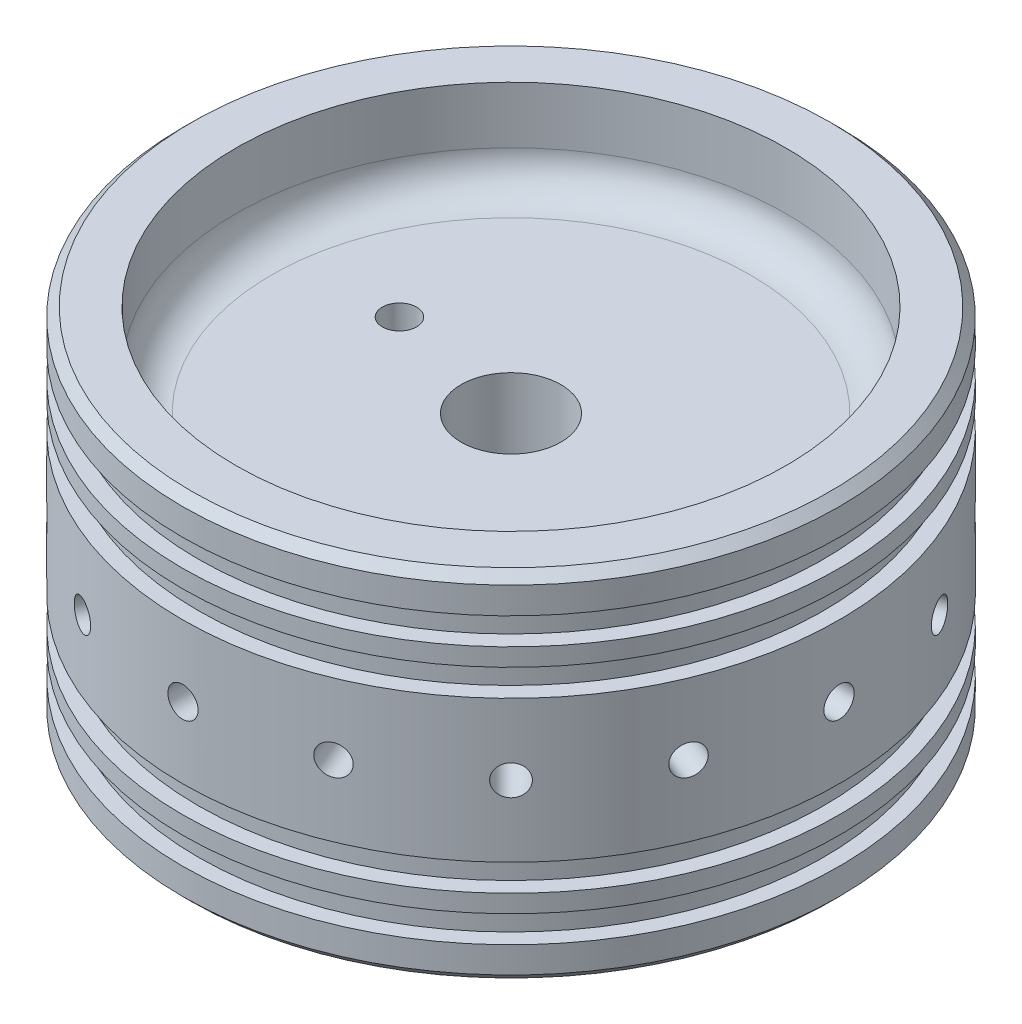
SolidWorks part; units mm, degrees
material "6061-T6 (SS)"
ref_plane "Front Plane" through (0, 0, 0) normal (0, 0, 1) x (1, 0, 0)
ref_plane "Top Plane" through (0, 0, 0) normal (0, 1, 0) x (1, 0, 0)
ref_plane "Right Plane" through (0, 0, 0) normal (1, 0, 0) x (0, 0, -1)
sketch "Sketch1" plane through (0, 0, 0) normal (0, 0, 1) x (1, 0, 0)
  line L11 (0, 0) -> (-58.7375, 0)
  line L13 (-58.7375, 31.8262) -> (-49.2125, 31.8262)
  line L14 (0, 0) -> (0, 15.3162)
  line L15 (0, 15.3162) -> (-49.2125, 15.3162)
  line L16 (-49.2125, 15.3162) -> (-49.2125, 31.8262)
  line L17 (0, 0) -> (0, -15.24)
  line L19 (-58.7375, -31.75) -> (-49.2125, -31.75)
  line L20 (-49.2125, -31.75) -> (-49.2125, -15.24)
  line L21 (-49.2125, -15.24) -> (0, -15.24)
  line L22 (0, 31.75) -> (0, -31.75) construction
  line L23 (-58.7375, 0) -> (-58.7375, 12.7)
  line L24 (-58.7375, 12.7) -> (-55.9181, 12.7)
  line L25 (-55.9181, 12.7) -> (-55.9181, 17.5006)
  line L26 (-55.9181, 17.5006) -> (-58.7375, 17.5006)
  line L27 (-58.7375, 17.5006) -> (-58.7375, 20.6756)
  line L28 (-58.7375, 20.6756) -> (-55.9181, 20.6756)
  line L29 (-55.9181, 20.6756) -> (-55.9181, 25.4762)
  line L30 (-55.9181, 25.4762) -> (-58.7375, 25.4762)
  line L31 (-58.7375, 25.4762) -> (-58.7375, 31.8262)
  line L32 (-58.7375, 0) -> (-58.7375, -12.7)
  line L33 (-58.7375, -12.7) -> (-55.9435, -12.7)
  line L34 (-55.9435, -12.7) -> (-55.9435, -17.5006)
  line L35 (-55.9435, -17.5006) -> (-58.7375, -17.5006)
  line L36 (-58.7375, -17.5006) -> (-58.7375, -20.6756)
  line L37 (-58.7375, -20.6756) -> (-55.9435, -20.6756)
  line L38 (-55.9435, -20.6756) -> (-55.9435, -25.4762)
  line L39 (-55.9435, -25.4762) -> (-58.7375, -25.4762)
  line L40 (-58.7375, -25.4762) -> (-58.7375, -31.75)
  dimension "D1" = 58.7375
  dimension "D2" = 12.7
  dimension "D3" = 4.8006
  dimension "D4" = 4.8006
  dimension "D5" = 3.175
  dimension "D6" = 2.8194
  dimension "D7" = 2.8194
  dimension "D8" = 9.525
  dimension "D9" = 12.7
  dimension "D10" = 4.8006
  dimension "D11" = 4.8006
  dimension "D12" = 3.175
  dimension "D13" = 2.794
  dimension "D14" = 2.794
  dimension "D16" = 9.525
revolve "Revolve1" add sketch "Sketch1" angle 360 about L22 region at (-32.4101, -9.7542, 0) region at (-32.3913, 9.7876, 0)
ref_plane "HoleFacePlane" through (0, 0, 58.7375) normal (0, 0, 1) x (1, 0, 0)
sketch "HoleReference" plane through (0, 0, 58.7375) normal (0, 0, 1) x (1, 0, 0)
  point P0 (0, 0)
hole_wizard "Tap Drill for 1/4-28 Tap1" positions "Sketch3" profile "Sketch4" hole size "1/4-28" standard "ANSI Inch"
sketch "Sketch3" plane through (0, 0, 58.7375) normal (0, 0, 1) x (1, 0, 0)
  point P0 (0, 0)
sketch "Sketch4" plane through (0, 0, 58.7375) normal (1, 0, 0) x (0, -1, 0)
  line L0 (0, 0) -> (0, 20.6754)
  line L1 (0, 20.6754) -> (2.7051, 19.05)
  line L2 (2.7051, 19.05) -> (2.7051, 0)
  line L5 (2.7051, 0) -> (0, 0)
  line L10 (0, 20.6754) -> (-2.7051, 19.05) construction
  line L11 (0, -6.35) -> (0, 107.95) construction
  dimension "Hole Dia." = 5.4102
  dimension "Hole Depth" = 19.05
  dimension "Drill Angle" = 118
ref_axis "Centerline" through (0, -12.7, 0) along (0, 1, 0)
pattern_circular "HolePattern" count 16 over 360 about axis through (0, -12.7, 0) along (0, 1, 0) of "Tap Drill for 1/4-28 Tap1"
chamfer "Chamfer2" distance 1.5875 angle 45 2 edges at (0, 31.8262, 58.7375) (0, -31.75, 58.7375)
fillet "Fillet1" radius 6.35 2 edges at (0, 15.3162, 49.2125) (0, -15.24, 49.2125)
sketch "CNVAReference" plane through (0, 15.3162, 0) normal (0, 1, 0) x (1, 0, 0)
  point P0 (0, 0)
sketch "InjectorReference" plane through (0, -15.24, 0) normal (0, -1, 0) x (1, 0, 0)
  point P0 (0, 0)
hole_wizard "Pipe Tap Drill for 1/2 Tap1" positions "Sketch7" profile "Sketch8" hole size "1/2" standard "ANSI Inch" end condition through all
sketch "Sketch7" plane through (0, 15.3162, 0) normal (0, 1, 0) x (1, 0, 0)
  point P0 (0, 0)
sketch "Sketch8" plane through (0, 15.3162, 0) normal (1, 0, 0) x (0, 0, 1)
  line L0 (0, 0) -> (0, 47.0662)
  line L1 (0, 47.0662) -> (8.9281, 47.0662)
  line L2 (8.9281, 47.0662) -> (8.9281, 0)
  line L5 (8.9281, 0) -> (0, 0)
  line L11 (0, -6.35) -> (0, 107.95) construction
  dimension "Thru Hole Dia." = 17.8562
  dimension "Thru Hole Depth" = 47.0662
sketch "CapillaryReference" plane through (0, 15.3162, 0) normal (0, 1, 0) x (1, 0, 0)
  line L0 (0, 0) -> (-31.0649, 0)
  line L1 (-24.9119, 4.9553) -> (0, 0)
  point P4 (-24.9119, 4.9553)
  dimension "D1" = 25.4
  dimension "D2" = 11.25
hole_wizard "Pipe Tap Drill for 1/16 Tap1" positions "Sketch10" profile "Sketch11" hole size "1/16" standard "ANSI Inch" end condition through all
sketch "Sketch10" plane through (0, 15.3162, 0) normal (0, 1, 0) x (1, 0, 0)
  point P0 (-24.9119, 4.9553)
sketch "Sketch11" plane through (-24.9119, 15.3162, -4.9553) normal (1, 0, 0) x (0, 0, 1)
  line L0 (0, 0) -> (0, 47.0662)
  line L1 (0, 47.0662) -> (3.0734, 47.0662)
  line L2 (3.0734, 47.0662) -> (3.0734, 0)
  line L5 (3.0734, 0) -> (0, 0)
  line L11 (0, -6.35) -> (0, 107.95) construction
  dimension "Thru Hole Dia." = 6.1468
  dimension "Thru Hole Depth" = 47.0662
